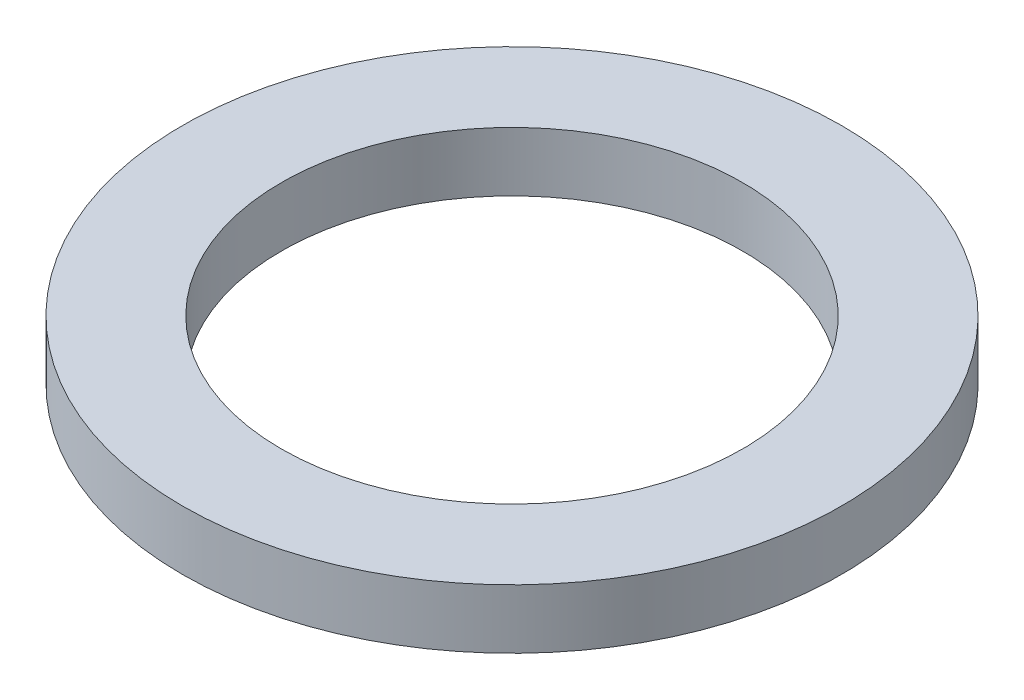
SolidWorks part; units mm, degrees
ref_plane "Front Plane" through (0, 0, 0) normal (0, 0, 1) x (1, 0, 0)
ref_plane "Top Plane" through (0, 0, 0) normal (0, 1, 0) x (1, 0, 0)
ref_plane "Right Plane" through (0, 0, 0) normal (1, 0, 0) x (0, 0, -1)
sketch "Sketch1" plane through (0, 0, 0) normal (0, 1, 0) x (1, 0, 0)
  circle A0 centre (0, 0) radius 50
  dimension "FLANGE_OD" = 100
extrude "Boss-Extrude1" add sketch "Sketch1" along normal blind 9
sketch "Sketch2" plane through (0, 0, 0) normal (0, 1, 0) x (1, 0, 0)
  circle A0 centre (0, 0) radius 35
  dimension "BORE_D" = 70
extrude "Cut-Extrude1" cut sketch "Sketch2" along normal through all
sketch "Sketch3" plane through (0, 9, 0) normal (0, 1, 0) x (1, 0, 0)
  circle A0 centre (0, 0) radius 21.3962 construction
  circle A1 centre (-21.3962, 0) radius 2.4423
  dimension "BOLT_D" = 4.8846
  dimension "BOLT_PCD" = 42.7924
extrude "Cut-Extrude2" cut sketch "Sketch3" against normal blind 5.8089 rebuild error yes
pattern_circular "CirPattern1" count 5 over 360 rebuild error yes
